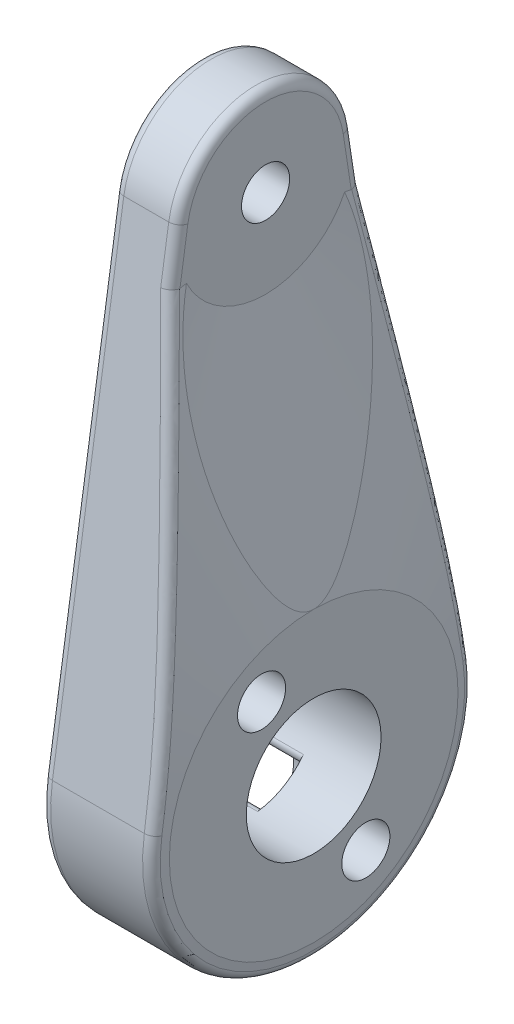
SolidWorks part; units mm, degrees
material "ABS"
ref_plane "Front" through (0, 0, 0) normal (0, 0, 1) x (1, 0, 0)
ref_plane "Top" through (0, 0, 0) normal (0, 1, 0) x (1, 0, 0)
ref_plane "Right" through (0, 0, 0) normal (1, 0, 0) x (0, 0, -1)
sketch "Esquisse1" plane through (0, 0, 0) normal (1, 0, 0) x (0, 0, -1)
  line L0 (-5.4378, 30.825) -> (-9.8869, 1.5)
  line L2 (5.4378, 30.825) -> (9.8869, 1.5)
  arc A0 (-9.8869, 1.5) -> (9.8869, 1.5) centre (0, 0) ccw
  arc A1 (5.4378, 30.825) -> (-5.4378, 30.825) centre (0, 30) ccw
  circle A2 centre (0, 30) radius 1.5
  circle A3 centre (0, 0) radius 4.2
  point P11 (0, 0)
  dimension "D1" = 3
  dimension "D2" = 11
  dimension "D3" = 8.4
  dimension "D4" = 20
  dimension "D5" = 30
extrude "Boss.-Extru.1" add sketch "Esquisse1" along normal blind 7
sketch "Esquisse2" plane through (7, 0, 0) normal (1, 0, 0) x (0, 0, -1)
  line L0 (-3.25, 5.6292) -> (3.25, -5.6292) construction
  line L1 (0, 50) -> (0, -50) construction
  circle A0 centre (-3.25, 5.6292) radius 1.5
  circle A1 centre (3.25, -5.6292) radius 1.5
  dimension "D1" = 3
  dimension "D2" = 30
  dimension "D3" = 13
extrude "Enlèv. mat.-Extru.1" cut sketch "Esquisse2" against normal through all
sketch "Esquisse3" plane through (0, 0, 0) normal (-1, 0, 0) x (0, 0, 1)
  circle A0 centre (3.25, 5.6292) radius 2.5
  circle A1 centre (-3.25, -5.6292) radius 2.5
  circle A2 centre (3.25, 5.6292) radius 1.5 construction
  circle A3 centre (-3.25, -5.6292) radius 1.5 construction
  dimension "D1" = 5
extrude "Enlèv. mat.-Extru.2" cut sketch "Esquisse3" against normal blind 3
fillet "Congé1" radius 0.4 4 edges at (1.5, -3.9654, -1.384) (1.5, -3.1813, -2.7422) (1.5, 3.1813, 2.7422) (1.5, 3.9654, 1.384)
sketch "Esquisse4" plane through (3, 0, 0) normal (-1, 0, 0) x (0, 0, 1)
  circle A0 centre (-3.25, -5.6292) radius 1.5 construction
  circle A1 centre (3.25, 5.6292) radius 1.5 construction
  circle A2 centre (-3.25, -5.6292) radius 1.5
  circle A3 centre (3.25, 5.6292) radius 1.5
extrude "Boss.-Extru.2" [suppressed] add sketch "Esquisse4" against normal blind 0.2
sketch "Esquisse5" plane through (0, 0, 0) normal (0, 0, 1) x (1, 0, 0)
  line L0 (0, 30.825) -> (0, 1.5) construction
  line L1 (7, 30) -> (4, 30)
  line L2 (7, 30) -> (7, 9)
  line L3 (7, 9) -> (4, 24.5)
  line L4 (4, 30) -> (4, 24.5)
  line L6 (7, 28.5) -> (7, 31.5) construction
  point P4 (1.777, 19.8743)
  point P8 (6.6847, 26.8775)
  dimension "D1" = 4
  dimension "D2" = 5.5
  dimension "D3" = 9
revolve "Enlèvement de matière-Révolution1" cut sketch "Esquisse5" angle 360 about L1
sketch "Esquisse6" plane through (0, 0, 0) normal (0, 0, 1) x (1, 0, 0)
  line L1 (7, 9) -> (4, 28)
  line L2 (7, 9) -> (7, 109)
  line L3 (7, 109) -> (4, 109)
  line L4 (4, 28) -> (4, 109)
  line L5 (7, 10.7873) -> (7, 1.5) construction
  line L6 (0, 30.825) -> (0, 1.5) construction
  line L8 (7, 0) -> (0, 0) construction
  line L9 (0, 31.5) -> (0, 28.5) construction
  point P4 (0, 0)
  point P5 (0, 0)
  point P10 (0, 0)
  point P14 (0, 30)
  dimension "D1" = 9
  dimension "D2" = 4
  dimension "D3" = 2
  dimension "D4" = 100
revolve "Enlèvement de matière-Révolution2" cut sketch "Esquisse6" angle 360 about L8
fillet "Congé2" radius 0.6 10 edges at (4, 29.0912, -5.7008) (4, 35.5, 0) (6.8421, -10, 0) (0, 35.5, 0) (0, 16.1625, -7.6623) (0, -10, 0) (4, 29.0912, 5.7008) (6.1812, 11.4475, 8.3777) (0, 16.1625, 7.6623)
sketch "Esquisse7" plane through (0, 0, 0) normal (-1, 0, 0) x (0, 0, 1)
  line L2 (9.2936, 1.41) -> (4.8446, 30.735)
  line L3 (-4.8446, 30.735) -> (-9.2936, 1.41)
  line L4 (9.2936, 1.41) -> (4.8446, 30.735)
  line L5 (-4.8446, 30.735) -> (-9.2936, 1.41)
  arc A2 (4.8446, 30.735) -> (-4.8446, 30.735) centre (0, 30) ccw
  arc A3 (-9.2936, 1.41) -> (9.2936, 1.41) centre (0, 0) ccw
  arc A4 (4.8446, 30.735) -> (-4.8446, 30.735) centre (0, 30) ccw
  arc A5 (-9.2936, 1.41) -> (9.2936, 1.41) centre (0, 0) ccw
  dimension "D1" = 0
extrude "Boss.-Extru.3" [suppressed] add sketch "Esquisse7" against normal blind 0.2
sketch "Esquisse8" plane through (7, 0, 0) normal (1, 0, 0) x (0, 0, -1)
  circle A1 centre (0, 0) radius 9
  circle A2 centre (0, 0) radius 9
  dimension "D1" = 0
extrude "Boss.-Extru.4" [suppressed] add sketch "Esquisse8" against normal blind 0.2
sketch "Esquisse9" [suppressed] plane through (4, 0, 0) normal (1, 0, 0) x (0, 0, -1)
  circle A0 centre (0, 30) radius 1.5 construction
  circle A1 centre (0, 30) radius 1.5
extrude "Boss.-Extru.5" [suppressed] add sketch "Esquisse9" against normal blind 0.2
